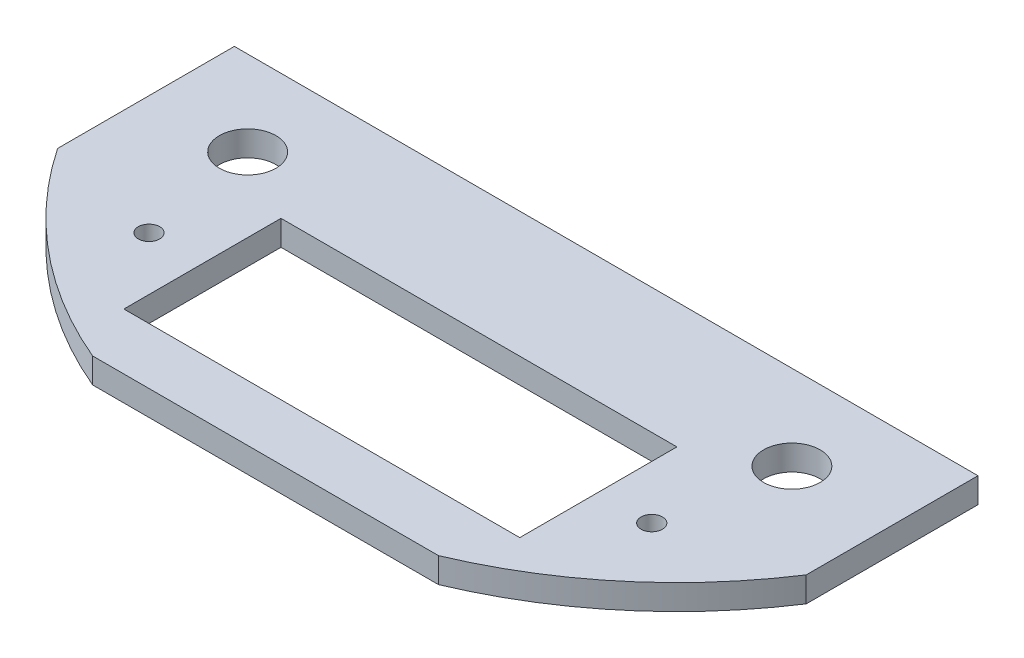
SolidWorks part; units mm, degrees
ref_plane "Plan de face" through (0, 0, 0) normal (0, 0, 1) x (1, 0, 0)
ref_plane "Plan de dessus" through (0, 0, 0) normal (0, 1, 0) x (1, 0, 0)
ref_plane "Plan de droite" through (0, 0, 0) normal (1, 0, 0) x (0, 0, -1)
sketch "Esquisse1" plane through (0, 0, 0) normal (0, 1, 0) x (1, 0, 0)
  line L0 (-58.9016, 6.7115) -> (-58.9016, 32.4862)
  line L1 (31.5, 12.5) -> (-31.5, 12.5)
  line L2 (31.5, 12.5) -> (31.5, -12.5)
  line L3 (31.5, -12.5) -> (-31.5, -12.5)
  line L4 (-31.5, 12.5) -> (-31.5, -12.5)
  line L5 (31.5, 12.5) -> (-31.5, -12.5) construction
  line L6 (31.5, -12.5) -> (-31.5, 12.5) construction
  line L7 (-58.9016, 32.4862) -> (59.4279, 32.4862)
  line L8 (59.4279, 32.4862) -> (59.4279, 7.4872)
  line L9 (0, 0) -> (0, 47.2436) construction
  line L10 (-58.9016, 6.7115) -> (0, 47.2436) construction
  line L11 (0, 47.2436) -> (59.4279, 7.4872) construction
  line L12 (-43.3, 22.2414) -> (43.3, 22.2414) construction
  line L13 (43.3, 22.2414) -> (0, 47.2436) construction
  line L14 (0, 47.2436) -> (-43.3, 22.2414) construction
  line L15 (-58.9016, 6.7115) -> (-58.9016, -21.4508)
  line L16 (-58.9016, -21.4508) -> (59.4279, -21.4508)
  line L17 (59.4279, -21.4508) -> (59.4279, 7.4872)
  point P8 (43.3, 22.2414)
  point P13 (0, 47.2436)
  point P14 (-43.3, 22.2414)
  point P16 (0, 22.2414)
  dimension "D3" = 71.5
  dimension "D1" = 25
  dimension "D2" = 63
  dimension "D4" = 50
  dimension "D5" = 86.6
extrude "Boss.-Extru.1" add sketch "Esquisse1" along normal blind 4
hole_wizard "Dégagement M81" positions "Esquisse2" profile "Esquisse4" hole size "M8" standard "DIN" end condition through all
sketch "Esquisse2" plane through (0, 4, 0) normal (0, 1, 0) x (1, 0, 0)
  line L0 (-43.3, 19) -> (0, 0) construction
  line L1 (0, 0) -> (43.3, 19) construction
  line L2 (43.3, 19) -> (-43.3, 19) construction
  point P0 (-43.3, 19)
  point P2 (43.3, 19)
  point P12 (-43.3, 18.8974)
  dimension "D1" = 86.6
  dimension "D2" = 19
sketch "Esquisse4" plane through (-43.3, 4, -19) normal (1, 0, 0) x (0, 0, 1)
  line L0 (0, 0) -> (0, 4)
  line L1 (0, 4) -> (4.5, 4)
  line L2 (4.5, 4) -> (4.5, 0)
  line L5 (4.5, 0) -> (0, 0)
  line L11 (0, -6.35) -> (0, 107.95) construction
  dimension "Diamètre du perçage jusqu'au prochain" = 9
  dimension "Profondeur du perçage jusqu'au prochain" = 4
sketch "Esquisse5" plane through (0, 4, 0) normal (0, 1, 0) x (1, 0, 0)
  line L0 (0, 44.0022) -> (0, 0) construction
  line L1 (-43.3, 19) -> (0, 44.0022) construction
  circle A0 centre (0, 44.0022) radius 71
  circle A1 centre (0, 44.0022) radius 96
  dimension "D1" = 25
  dimension "D3" = 142
  dimension "D2" = 50
extrude "Enlèv. mat.-Extru.1" cut sketch "Esquisse5" against normal through all
hole_wizard "Dégagement M31" positions "Esquisse7" profile "Esquisse8" hole size "M3" standard "DIN" end condition through all
sketch "Esquisse7" plane through (0, 0, 0) normal (0, -1, 0) x (-1, 0, 0)
  line L0 (-40, 0) -> (40, 0) construction
  circle A0 centre (-40, 0) radius 5 construction
  circle A1 centre (40, 0) radius 5 construction
  point P0 (-40, 0)
  point P2 (40, 0)
  dimension "D2" = 10
  dimension "D1" = 80
sketch "Esquisse8" plane through (40, 0, 0) normal (1, 0, 0) x (0, 0, -1)
  line L0 (0, 0) -> (0, 4)
  line L1 (0, 4) -> (1.7, 4)
  line L2 (1.7, 4) -> (1.7, 0)
  line L5 (1.7, 0) -> (0, 0)
  line L11 (0, -6.35) -> (0, 107.95) construction
  dimension "Diamètre du perçage jusqu'au prochain" = 3.4
  dimension "Profondeur du perçage jusqu'au prochain" = 4
